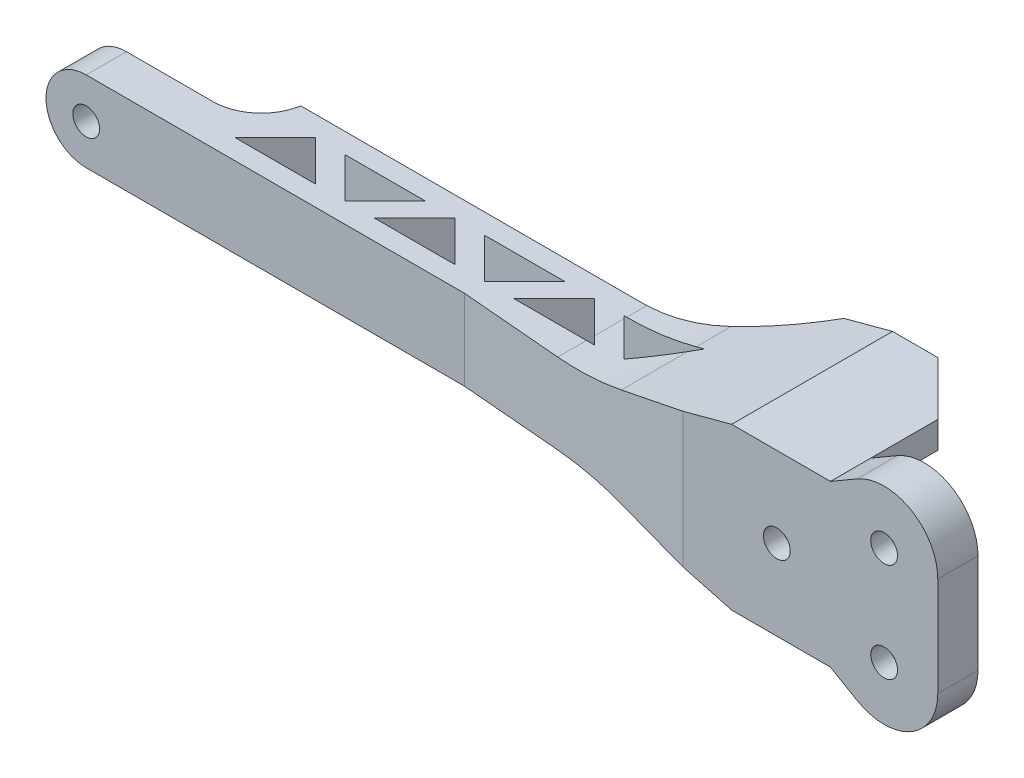
SolidWorks part; units mm, degrees
ref_plane "Front Plane" through (0, 0, 0) normal (0, 0, 1) x (1, 0, 0)
ref_plane "Top Plane" through (0, 0, 0) normal (0, 1, 0) x (1, 0, 0)
ref_plane "Right Plane" through (0, 0, 0) normal (1, 0, 0) x (0, 0, -1)
sketch "Sketch1" plane through (0, 0, 0) normal (0, 1, 0) x (1, 0, 0)
  line L0 (0, 0) -> (126.4393, 0)
  line L1 (180, 22.5) -> (215, 22.5)
  line L2 (215, 22.5) -> (235, 2.5)
  line L3 (235, 2.5) -> (235, -22.5)
  line L4 (235, -22.5) -> (275, -22.5)
  line L5 (275, -22.5) -> (275, -37.5)
  line L6 (275, -37.5) -> (180, -37.5)
  line L7 (180, -37.5) -> (91, -30)
  line L8 (91, -30) -> (-65, -30)
  line L9 (-65, -30) -> (-65, -15)
  line L10 (-65, -15) -> (-17.7482, -15)
  line L11 (-65, -22.5) -> (235, -22.5) construction
  line L12 (215, -37.5) -> (215, -8.413) construction
  line L13 (255, -37.5) -> (255, -8.413) construction
  line L14 (-2, -22.5) -> (13, -7.5)
  line L15 (13, -7.5) -> (28, -22.5)
  line L16 (28, -22.5) -> (-2, -22.5)
  line L17 (50, -22.5) -> (65, -7.5)
  line L18 (65, -7.5) -> (80, -22.5)
  line L19 (80, -22.5) -> (50, -22.5)
  line L20 (54, -7.5) -> (39, -22.5)
  line L21 (39, -22.5) -> (24, -7.5)
  line L22 (24, -7.5) -> (54, -7.5)
  line L23 (106, -7.5) -> (91, -22.5)
  line L24 (91, -22.5) -> (76, -7.5)
  line L25 (76, -7.5) -> (106, -7.5)
  line L26 (158, -7.5) -> (143, -22.5)
  line L27 (143, -22.5) -> (128, -7.5)
  line L28 (128, -7.5) -> (158, -7.5)
  line L29 (102, -22.5) -> (117, -7.5)
  line L30 (117, -7.5) -> (132, -22.5)
  line L31 (132, -22.5) -> (102, -22.5)
  line L32 (-50, -22.5) -> (-50, -7.5) construction
  arc A0 (126.4393, 0) -> (180, 22.5) centre (126.4393, 75) ccw
  arc A1 (-17.7482, -15) -> (0, 0) centre (-17.7482, 3) ccw
  dimension "D1" = 75
  dimension "D6" = 18
  dimension "D2" = 245
  dimension "D3" = 15
  dimension "D4" = 30
  dimension "D5" = 65
  dimension "D7" = 60
  dimension "D8" = 15
  dimension "D9" = 20
  dimension "D10" = 300
  dimension "D11" = 60
  dimension "D12" = 15
  dimension "D13" = 45
  dimension "D14" = 325
  dimension "D15" = 11
  dimension "D16" = 30
  dimension "D17" = 63
  dimension "D18" = 11
  dimension "D19" = 11
  dimension "D20" = 11
  dimension "D21" = 11
extrude "Boss-Extrude1" add sketch "Sketch1" along normal blind 77
sketch "Sketch2" plane through (0, 0, 0) normal (0, 0, -1) x (-1, 0, 0)
  line L0 (65, 38.5) -> (-275, 38.5) construction
  line L1 (65, 77) -> (65, 0) construction
  line L2 (-275, 77) -> (-275, 0) construction
  line L3 (-154.8819, 20.0926) -> (-198.146, 8.5)
  line L4 (50, 23.5) -> (-129, 23.5)
  line L5 (50, 23.5) -> (50, 53.5)
  line L6 (50, 53.5) -> (-129, 53.5)
  line L7 (-129, 23.5) -> (-129, 53.5)
  line L8 (-198.146, 8.5) -> (-235, 8.5)
  line L9 (-235, 8.5) -> (-235, 18.5)
  line L10 (-235, 18.5) -> (-205, 18.5)
  line L11 (-190, 33.5) -> (-190, 57.3352) construction
  line L12 (-255, 57) -> (-255, 20) construction
  line L13 (-235, 57) -> (-235, 20)
  line L14 (-275, 57) -> (-275, 20)
  line L15 (-244.9389, 2.7149) -> (-235, 8.5)
  line L16 (-244.9389, 74.2851) -> (-235, 68.5)
  line L17 (-235, 68.5) -> (-235, 58.5)
  line L18 (-235, 58.5) -> (-205, 58.5)
  line L19 (-198.146, 68.5) -> (-235, 68.5)
  line L20 (-154.8819, 56.9074) -> (-198.146, 68.5)
  line L21 (-190, 33.5) -> (-190, 43.5)
  line L22 (65, 0) -> (65, 77)
  line L23 (65, 77) -> (-275, 77)
  line L24 (-275, 77) -> (-275, 0)
  line L25 (-275, 0) -> (65, 0)
  circle A0 centre (50, 38.5) radius 15
  arc A1 (-129, 23.5) -> (-154.8819, 20.0926) centre (-129, -76.5) ccw
  arc A2 (-205, 18.5) -> (-190, 33.5) centre (-205, 33.5) ccw
  arc A3 (-235, 57) -> (-275, 57) centre (-255, 57) ccw
  arc A4 (-275, 20) -> (-235, 20) centre (-255, 20) ccw
  arc A5 (-205, 58.5) -> (-190, 43.5) centre (-205, 43.5) cw
  arc A6 (-129, 53.5) -> (-154.8819, 56.9074) centre (-129, 153.5) cw
  point P22 (-255, 38.5)
  line M9 (-126.4393, 0) -> (0, 0)
  line M10 (0, 0) -> (0, 77)
  line M11 (0, 77) -> (-126.4393, 77)
  line M12 (-126.4393, 77) -> (-126.4393, 0)
  dimension "D1" = 30
  dimension "D3" = 100
  dimension "D4" = 15
  dimension "D8" = 45
  dimension "D10" = 20
  dimension "D11" = 77
  dimension "D2" = 179
  dimension "D5" = 165
  dimension "D6" = 20
  dimension "D7" = 30
  dimension "D9" = 300
extrude "Cut-Extrude1" cut sketch "Sketch2" against normal through all both and the other way through all contours L4 M10 M12 M9 | A0 L4 L25 L22 M10 | A0 L22 L23 L6 M10 | L6 M10 M11 M12 | A6 L6 L23 A3 L16 L19 L20 M12 | A4 L25 L4 A1 L3 L8 L15 M12 | A4 L24 L25 | A3 L23 L24 region at (171.4464, 8.1743, 0) region at (63.2196, 11.75, 0) region at (171.4464, 68.8257, 0) region at (-33.3932, 12.2127, 0) region at (63.2196, 65.25, 0) region at (270.5326, 4.4674, 0) region at (-33.3932, 64.7873, 0) region at (270.5326, 72.5326, 0)
extrude "Cut-Extrude2" cut sketch "Sketch2<3>" against normal up to surface (22.5 mm away) and the other way through all contours A5 L18 L17 L16 A3 L13 A4 L15 L9 L10 A2 L21 region at (214.1581, 38.5, 0) up to face at (253.313, 38.5, 22.5)
sketch "Sketch2<3>" plane through (0, 0, 0) normal (0, 0, -1) x (-1, 0, 0) same geometry as "Sketch2"
sketch "Sketch3" plane through (0, 0, 22.5) normal (0, 0, -1) x (-1, 0, 0)
  line L0 (-275, 38.5) -> (97.8605, 38.5) construction
  line L1 (-275, 57) -> (-275, 20) construction
  line L3 (-235, 8.5) -> (-215, 8.5) construction
  circle A0 centre (-215, 38.5) radius 5
  circle A1 centre (-255, 20.04) radius 5
  circle A2 centre (-255, 56.96) radius 5
  circle A3 centre (50, 38.5) radius 5
  dimension "D4" = 10
  dimension "D5" = 11.54
  dimension "D2" = 20
  dimension "D3" = 60
extrude "Cut-Extrude3" cut sketch "Sketch3" against normal through all and the other way through all
sketch "Sketch4" plane through (0, 0, 22.5) normal (0, 0, -1) x (-1, 0, 0)
  circle A0 centre (-215, 38.5) radius 5 construction
  circle A1 centre (-255, 20.04) radius 5 construction
  circle A2 centre (-255, 56.96) radius 5 construction
  circle A3 centre (-215, 38.5) radius 5
  circle A4 centre (-255, 20.04) radius 5
  circle A5 centre (-255, 56.96) radius 5
  circle A6 centre (-215, 38.5) radius 7.5
  circle A7 centre (-255, 20.04) radius 7.5
  circle A8 centre (-255, 56.96) radius 7.5
  dimension "D1" = 2.5
extrude "Cut-Extrude4" cut sketch "Sketch4" against normal blind 8
